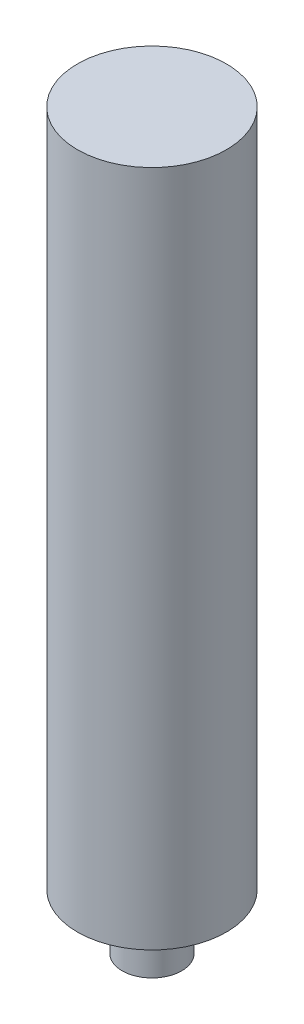
SolidWorks part; units mm, degrees
ref_plane "Front Plane" through (0, 0, 0) normal (0, 0, 1) x (1, 0, 0)
ref_plane "Top Plane" through (0, 0, 0) normal (0, 1, 0) x (1, 0, 0)
ref_plane "Right Plane" through (0, 0, 0) normal (1, 0, 0) x (0, 0, -1)
sketch "Sketch1" plane through (0, 0, 0) normal (0, 1, 0) x (1, 0, 0)
  circle A0 centre (0, 0) radius 40
extrude "Boss-Extrude1" add sketch "Sketch1" along normal blind 364
sketch "Sketch2" plane through (0, 0, 0) normal (0, -1, 0) x (1, 0, 0)
  circle A0 centre (0, 0) radius 16
extrude "Boss-Extrude2" add sketch "Sketch2" along normal blind 30 contours A0
